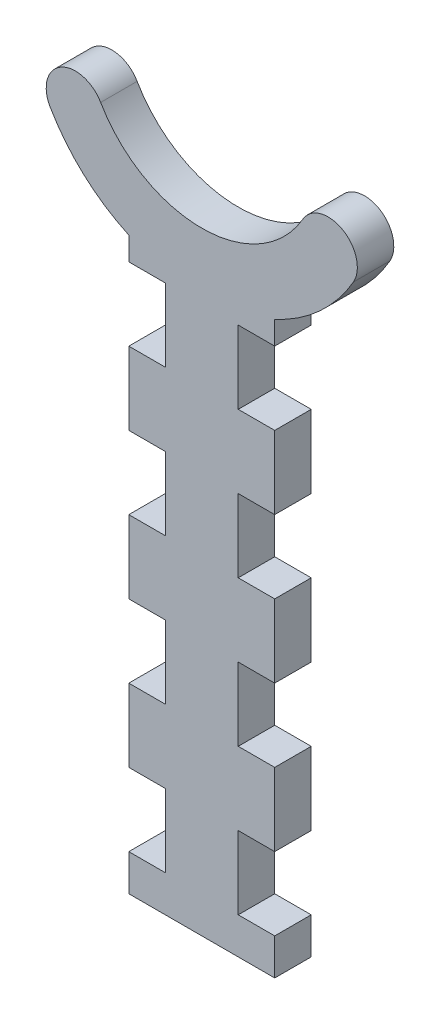
SolidWorks part; units mm, degrees
material "ﾁｰｸ材"
ref_plane "正面" through (0, 0, 0) normal (0, 0, 1) x (1, 0, 0)
ref_plane "平面" through (0, 0, 0) normal (0, 1, 0) x (1, 0, 0)
ref_plane "右側面" through (0, 0, 0) normal (1, 0, 0) x (0, 0, -1)
sketch "ｽｹｯﾁ1" plane through (0, 0, 0) normal (0, 0, 1) x (1, 0, 0)
  line L0 (-10, -21.8174) -> (-10, -100)
  line L1 (-10, -100) -> (10, -100)
  line L2 (10, -100) -> (10, -21.8174)
  arc A0 (-13.8564, -8) -> (13.8564, -8) centre (0, 0) ccw
  arc A1 (13.8564, -8) -> (20.7846, -12) centre (17.3205, -10) cw
  arc A2 (20.7846, -12) -> (10, -21.8174) centre (0, 0) cw
  arc A3 (-20.7846, -12) -> (-13.8564, -8) centre (-17.3205, -10) cw
  arc A4 (-10, -21.8174) -> (-20.7846, -12) centre (0, 0) cw
  point P8 (10, -21.8174)
  point P9 (0, -100)
  point P12 (10, -21.8174)
  point P15 (-10, -21.8174)
  dimension "D1" = 16
  dimension "D2" = 24
  dimension "D3" = 120
  dimension "D5" = 20
  dimension "D4" = 100
extrude "ﾎﾞｽ - 押し出し1" add sketch "ｽｹｯﾁ1" along normal blind 5
sketch "ｽｹｯﾁ2" plane through (0, 0, 5) normal (0, 0, 1) x (1, 0, 0)
  line L0 (10, -100) -> (10, -21.8174) construction
  line L1 (10, -95) -> (5, -95)
  line L2 (10, -95) -> (10, -85)
  line L3 (10, -85) -> (5, -85)
  line L4 (5, -95) -> (5, -85)
  line L5 (-10, -100) -> (10, -100) construction
  line L6 (10, -75) -> (10, -65)
  line L7 (10, -75) -> (5, -75)
  line L8 (5, -75) -> (5, -65)
  line L9 (10, -65) -> (5, -65)
  line L10 (10, -55) -> (10, -45)
  line L11 (10, -55) -> (5, -55)
  line L12 (5, -55) -> (5, -45)
  line L13 (10, -45) -> (5, -45)
  line L14 (10, -35) -> (10, -25)
  line L15 (10, -35) -> (5, -35)
  line L16 (5, -35) -> (5, -25)
  line L17 (10, -25) -> (5, -25)
  line L18 (0, -100) -> (0, -83.6245) construction
  line L19 (-10, -85) -> (-5, -85)
  line L20 (-5, -95) -> (-5, -85)
  line L21 (-10, -95) -> (-5, -95)
  line L22 (-10, -95) -> (-10, -85)
  line L23 (-10, -75) -> (-5, -75)
  line L24 (-5, -75) -> (-5, -65)
  line L25 (-10, -65) -> (-5, -65)
  line L26 (-10, -75) -> (-10, -65)
  line L27 (-10, -55) -> (-5, -55)
  line L28 (-5, -55) -> (-5, -45)
  line L29 (-10, -45) -> (-5, -45)
  line L30 (-10, -55) -> (-10, -45)
  line L31 (-10, -35) -> (-5, -35)
  line L32 (-5, -35) -> (-5, -25)
  line L33 (-10, -25) -> (-5, -25)
  line L34 (-10, -35) -> (-10, -25)
  dimension "D1" = 5
  dimension "D2" = 10
  dimension "D3" = 5
  dimension "D4" = 4
extrude "ｶｯﾄ - 押し出し1" cut sketch "ｽｹｯﾁ2" against normal through all
